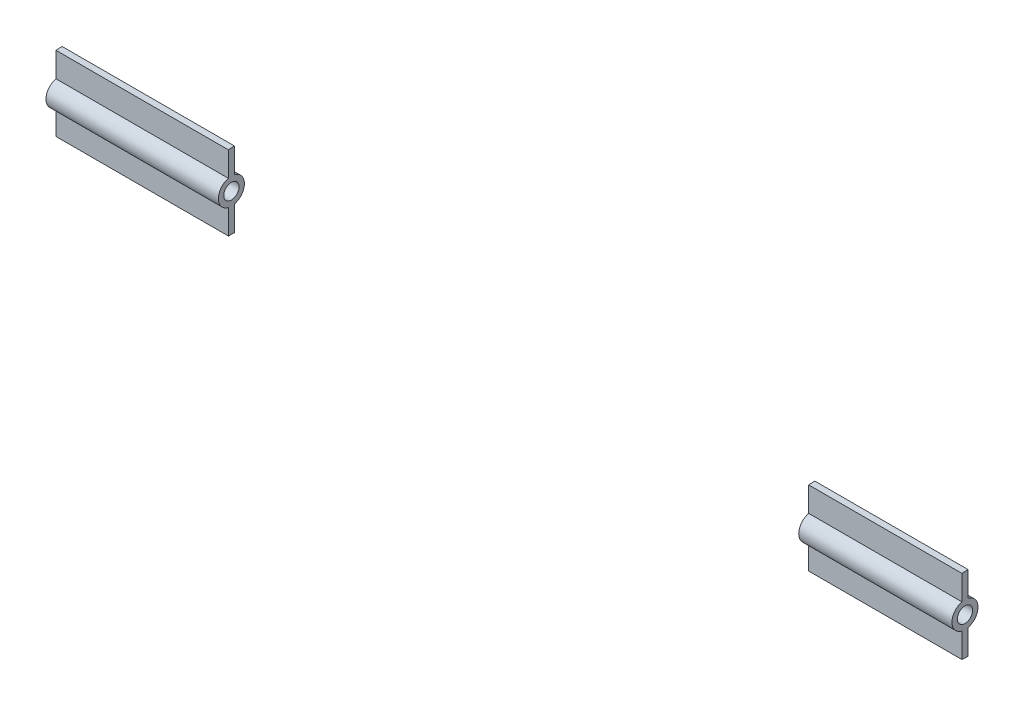
SolidWorks part; units mm, degrees
material "ABS"
ref_plane "Front Plane" through (0, 0, 0) normal (0, 0, 1) x (1, 0, 0)
ref_plane "Top Plane" through (0, 0, 0) normal (0, 1, 0) x (1, 0, 0)
ref_plane "Right Plane" through (0, 0, 0) normal (1, 0, 0) x (0, 0, -1)
body saved out of another part "Stock-V-tail-1" rebuild error yes
ref_plane "Plane1" through (235.5, 0, 0) normal (1, 0, 0) x (0, 0, -1)
sketch "Sketch2" plane through (235.5, 0, 0) normal (1, 0, 0) x (0, 0, -1)
  arc A1 (-136.0381, -9.253) -> (-136.0381, 9.253) centre (-141.8338, 0) ccw construction
  arc A3 (-136.0381, -9.253) -> (-136.0381, 9.253) centre (-141.8338, 0) ccw
  circle A4 centre (-62, 0) radius 9 construction
  circle A5 centre (-62, 0) radius 9
  spline S0 degree 3 poles (-248, 0) (-248, 0.0474) (-245.7346, 0.2359) (-243.4112, 0.6292) (-237.7674, 1.2323) (-230.8332, 1.9808) (-221.7981, 2.8592) (-211.1903, 3.8286) (-199.0563, 4.8702) (-185.65, 5.9536) (-171.1852, 7.0355) (-155.914, 8.0839) (-140.0967, 9.0504) (-124.0041, 9.8942) (-107.9109, 10.5652) (-94.6227, 10.9527) (-84.1989, 11.1308) (-76.6156, 11.194) (-69.2347, 11.1852) (-62.0877, 11.0901) (-55.2058, 10.9234) (-48.6191, 10.6715) (-42.3552, 10.3437) (-36.4402, 9.9323) (-30.8991, 9.4444) (-25.7573, 8.8756) (-21.0365, 8.2367) (-16.7549, 7.5443) (-12.9305, 6.8014) (-9.5757, 6.0106) (-6.7064, 5.1453) (-4.3287, 4.1895) (-2.4645, 3.1349) (-1.1239, 2.0336) (-0.2866, 1.0243) (0.1173, 0) (-0.2866, -1.0243) (-1.1239, -2.0336) (-2.4645, -3.1349) (-4.3287, -4.1895) (-6.7064, -5.1453) (-9.5757, -6.0106) (-12.9305, -6.8014) (-16.7549, -7.5443) (-21.0365, -8.2367) (-25.7573, -8.8756) (-30.8991, -9.4444) (-36.4402, -9.9323) (-42.3552, -10.3437) (-48.6191, -10.6715) (-55.2058, -10.9234) (-62.0877, -11.0901) (-69.2347, -11.1852) (-76.6156, -11.194) (-84.1989, -11.1308) (-94.6227, -10.9527) (-107.9109, -10.5652) (-124.0041, -9.8942) (-140.0967, -9.0504) (-155.914, -8.0839) (-171.1852, -7.0355) (-185.65, -5.9536) (-199.0563, -4.8702) (-211.1903, -3.8286) (-221.7981, -2.8592) (-230.8332, -1.9808) (-237.7674, -1.2323) (-243.4112, -0.6292) (-245.7346, -0.2359) (-248, -0.0474) (-248, 0) (-248, 0.0474) (-245.7346, 0.2359) knots -0.002133 0 0 0 0.002133 0.008488 0.018944 0.033319 0.051356 0.072756 0.097141 0.124097 0.153163 0.183834 0.215589 0.247878 0.280151 0.31186 0.327333 0.342463 0.357187 0.371448 0.385183 0.398331 0.410845 0.422673 0.433769 0.44409 0.453589 0.46224 0.47001 0.476871 0.482833 0.487909 0.492155 0.495592 0.498196 0.5 0.501804 0.504408 0.507845 0.512091 0.517167 0.523129 0.52999 0.53776 0.546411 0.55591 0.566231 0.577327 0.589155 0.601669 0.614817 0.628552 0.642813 0.657537 0.672667 0.68814 0.719849 0.752122 0.784411 0.816166 0.846837 0.875903 0.902859 0.927244 0.948644 0.966681 0.981056 0.991512 0.997867 1 1 1 1.002133 1.008488 1.018944 only from (-136.0381, 9.253) to (-136.0381, -9.253) construction
  spline S1 degree 3 poles (-136.0381, 9.253) (-132.0261, 9.4717) (-122.621, 9.9519) (-107.9109, 10.5652) (-94.6227, 10.9527) (-84.1989, 11.1308) (-76.6156, 11.194) (-69.2347, 11.1852) (-62.0877, 11.0901) (-55.2058, 10.9234) (-48.6191, 10.6715) (-42.3552, 10.3437) (-36.4402, 9.9323) (-30.8991, 9.4444) (-25.7573, 8.8756) (-21.0365, 8.2367) (-16.7549, 7.5443) (-12.9305, 6.8014) (-9.5757, 6.0106) (-6.7064, 5.1453) (-4.3287, 4.1895) (-2.4645, 3.1349) (-1.1239, 2.0336) (-0.2866, 1.0243) (0.1173, 0) (-0.2866, -1.0243) (-1.1239, -2.0336) (-2.4645, -3.1349) (-4.3287, -4.1895) (-6.7064, -5.1453) (-9.5757, -6.0106) (-12.9305, -6.8014) (-16.7549, -7.5443) (-21.0365, -8.2367) (-25.7573, -8.8756) (-30.8991, -9.4444) (-36.4402, -9.9323) (-42.3552, -10.3437) (-48.6191, -10.6715) (-55.2058, -10.9234) (-62.0877, -11.0901) (-69.2347, -11.1852) (-76.6156, -11.194) (-84.1989, -11.1308) (-94.6227, -10.9527) (-107.9109, -10.5652) (-122.621, -9.9519) (-132.0261, -9.4717) (-136.0381, -9.253) knots 0.223863 0.223863 0.223863 0.223863 0.247878 0.280151 0.31186 0.327333 0.342463 0.357187 0.371448 0.385183 0.398331 0.410845 0.422673 0.433769 0.44409 0.453589 0.46224 0.47001 0.476871 0.482833 0.487909 0.492155 0.495592 0.498196 0.5 0.501804 0.504408 0.507845 0.512091 0.517167 0.523129 0.52999 0.53776 0.546411 0.55591 0.566231 0.577327 0.589155 0.601669 0.614817 0.628552 0.642813 0.657537 0.672667 0.68814 0.719849 0.752122 0.776137 0.776137 0.776137 0.776137
extrude "Boss-Extrude1" add sketch "Sketch2" along normal up to surface (1 mm away) rebuild error yes
sketch "Sketch4" plane through (236.5, 0, 0) normal (1, 0, 0) x (0, 0, -1)
  line L0 (-117, 9.7778) -> (-117, -9.7778) construction
  line L1 (-117.8, 9.7438) -> (-117.8, 3.3045)
  line L2 (-116.2, 9.8114) -> (-116.2, 3.3045)
  line L3 (-117.8, 9.7438) -> (-116.2, 9.8114)
  line L4 (-116.2, -9.8114) -> (-116.2, -3.3045)
  line L5 (-117.8, -9.7438) -> (-117.8, -3.3045)
  line L6 (-116.2, -9.8114) -> (-117.8, -9.7438)
  circle A4 centre (-62, 0) radius 9 construction
  circle A5 centre (-62, 0) radius 9 construction
  circle A6 centre (-117, 0) radius 2
  arc A7 (-116.2, -3.3045) -> (-116.2, 3.3045) centre (-117, 0) ccw
  arc A8 (-117.8, 3.3045) -> (-117.8, -3.3045) centre (-117, 0) ccw
  spline S7 degree 1 poles (-136.0163, 8.8536) (-136.0163, -8.8536) knots 0 0 1 1 construction
  spline S8 degree 3 poles (-136.0163, 8.8536) (-130.2514, 9.1678) (-124.2459, 9.4651) (-118.1056, 9.7307) (-117.6666, 9.7495) (-117.4, 9.7609) (-117.1333, 9.7722) (-116.8666, 9.7835) (-116.6, 9.7947) (-116.3333, 9.8058) (-111.2706, 10.0168) (-100.5041, 10.4086) (-84.0958, 10.7773) (-69.6656, 10.8196) (-58.1244, 10.6127) (-49.4737, 10.3215) (-40.8313, 9.8647) (-33.6424, 9.3078) (-27.907, 8.7199) (-23.6162, 8.1931) (-19.3389, 7.5713) (-15.0835, 6.8329) (-11.5652, 6.0893) (-8.7915, 5.3615) (-6.7466, 4.7182) (-4.7593, 3.9358) (-2.8953, 2.9508) (-1.5069, 1.8551) (-0.7638, 0.969) (-0.4573, 0.3737) (-0.3714, 0) (-0.4573, -0.3737) (-0.7638, -0.969) (-1.5069, -1.8551) (-2.8953, -2.9508) (-4.7593, -3.9358) (-6.7466, -4.7182) (-8.7915, -5.3615) (-11.5652, -6.0893) (-15.0835, -6.8329) (-19.3389, -7.5713) (-23.6162, -8.1931) (-27.907, -8.7199) (-33.6424, -9.3078) (-40.8313, -9.8647) (-49.4737, -10.3215) (-58.1244, -10.6127) (-69.6656, -10.8196) (-84.0958, -10.7773) (-100.5041, -10.4086) (-111.2706, -10.0168) (-116.3333, -9.8058) (-116.6, -9.7947) (-116.8666, -9.7835) (-117.1333, -9.7722) (-117.4, -9.7609) (-117.6666, -9.7495) (-118.1056, -9.7307) (-124.2459, -9.4651) (-130.2514, -9.1678) (-136.0163, -8.8536) knots 0 0 0 0 0.0625 0.065089 0.066534 0.067256 0.067979 0.069423 0.070146 0.070868 0.072313 0.125 0.1875 0.25 0.28125 0.3125 0.34375 0.375 0.390625 0.40625 0.421875 0.4375 0.453125 0.460938 0.46875 0.476562 0.484375 0.492188 0.496094 0.498047 0.5 0.501953 0.503906 0.507812 0.515625 0.523438 0.53125 0.539062 0.546875 0.5625 0.578125 0.59375 0.609375 0.625 0.65625 0.6875 0.71875 0.75 0.8125 0.875 0.927687 0.929132 0.929854 0.930577 0.932021 0.932744 0.933466 0.934911 0.9375 1 1 1 1 construction
  spline S13 degree 3 poles (-1848.5448, 5455.4948) (-1254.8548, -370.5463) (-691.9533, -13.7835) (-107.9109, 10.5652) (-94.6227, 10.9527) (-84.1989, 11.1308) (-76.6156, 11.194) (-69.2347, 11.1852) (-62.0877, 11.0901) (-55.2058, 10.9234) (-48.6191, 10.6715) (-42.3552, 10.3437) (-36.4402, 9.9323) (-30.8991, 9.4444) (-25.7573, 8.8756) (-21.0365, 8.2367) (-16.7549, 7.5443) (-12.9305, 6.8014) (-9.5757, 6.0106) (-6.7064, 5.1453) (-4.3287, 4.1895) (-2.4645, 3.1349) (-1.1239, 2.0336) (-0.2866, 1.0243) (0.1173, 0) (-0.2866, -1.0243) (-1.1239, -2.0336) (-2.4645, -3.1349) (-4.3287, -4.1895) (-6.7064, -5.1453) (-9.5757, -6.0106) (-12.9305, -6.8014) (-16.7549, -7.5443) (-21.0365, -8.2367) (-25.7573, -8.8756) (-30.8991, -9.4444) (-36.4402, -9.9323) (-42.3552, -10.3437) (-48.6191, -10.6715) (-55.2058, -10.9234) (-62.0877, -11.0901) (-69.2347, -11.1852) (-76.6156, -11.194) (-84.1989, -11.1308) (-94.6227, -10.9527) (-107.9109, -10.5652) (-691.9613, 13.7839) (-1254.8704, 370.5562) (-1848.5696, -5455.7381) knots -6.166881 -6.166881 -6.166881 -6.166881 0.043484 0.10192 0.159336 0.187352 0.214748 0.241409 0.267232 0.292102 0.315909 0.338567 0.359984 0.380076 0.398764 0.415965 0.431629 0.445697 0.45812 0.468916 0.478106 0.485795 0.492019 0.496734 0.5 0.503266 0.507981 0.514205 0.521894 0.531084 0.54188 0.554303 0.568371 0.584035 0.601236 0.619924 0.640016 0.661433 0.684091 0.707898 0.732768 0.758591 0.785252 0.812648 0.840664 0.89808 0.956516 7.166968 7.166968 7.166968 7.166968 only from (-136.0381, 9.253) to (-136.0381, -9.253)
  spline S14 degree 3 poles (-136.0381, 9.253) (-132.0261, 9.4717) (-122.621, 9.9519) (-107.9109, 10.5652) (-94.6227, 10.9527) (-84.1989, 11.1308) (-76.6156, 11.194) (-69.2347, 11.1852) (-62.0877, 11.0901) (-55.2058, 10.9234) (-48.6191, 10.6715) (-42.3552, 10.3437) (-36.4402, 9.9323) (-30.8991, 9.4444) (-25.7573, 8.8756) (-21.0365, 8.2367) (-16.7549, 7.5443) (-12.9305, 6.8014) (-9.5757, 6.0106) (-6.7064, 5.1453) (-4.3287, 4.1895) (-2.4645, 3.1349) (-1.1239, 2.0336) (-0.2866, 1.0243) (0.1173, 0) (-0.2866, -1.0243) (-1.1239, -2.0336) (-2.4645, -3.1349) (-4.3287, -4.1895) (-6.7064, -5.1453) (-9.5757, -6.0106) (-12.9305, -6.8014) (-16.7549, -7.5443) (-21.0365, -8.2367) (-25.7573, -8.8756) (-30.8991, -9.4444) (-36.4402, -9.9323) (-42.3552, -10.3437) (-48.6191, -10.6715) (-55.2058, -10.9234) (-62.0877, -11.0901) (-69.2347, -11.1852) (-76.6156, -11.194) (-84.1989, -11.1308) (-94.6227, -10.9527) (-107.9109, -10.5652) (-122.621, -9.9519) (-132.0261, -9.4717) (-136.0381, -9.253) knots 0 0 0 0 0.043484 0.10192 0.159336 0.187352 0.214748 0.241409 0.267232 0.292102 0.315909 0.338567 0.359984 0.380076 0.398764 0.415965 0.431629 0.445697 0.45812 0.468916 0.478106 0.485795 0.492019 0.496734 0.5 0.503266 0.507981 0.514205 0.521894 0.531084 0.54188 0.554303 0.568371 0.584035 0.601236 0.619924 0.640016 0.661433 0.684091 0.707898 0.732768 0.758591 0.785252 0.812648 0.840664 0.89808 0.956516 1 1 1 1 construction
  dimension "D1" = 55
  dimension "D2" = 4
  dimension "D3" = 6.8
  dimension "D9" = 6.5069
  dimension "D5" = 0.8
  dimension "D6" = 0.8
  dimension "D7" = 0.8
  dimension "D8" = 0.8
  dimension "D4" = 0.4
extrude "Cut-Extrude2" cut sketch "Sketch4" against normal blind 44 contours A6 rebuild error yes
extrude "Boss-Extrude3" add sketch "Sketch4<4>" against normal blind 40
sketch "Sketch4<4>" plane through (236.5, 0, 0) normal (1, 0, 0) x (0, 0, -1) same geometry as "Sketch4"
sketch "Sketch9" plane through (0, 0, 0) normal (-1, 0, 0) x (0, 0, 1)
  line L0 (116.2, 9.8115) -> (116.2, 3.3045)
  line L1 (117, 9.778) -> (117, -9.7778) construction
  line L2 (117.8, 9.744) -> (117.8, 3.3045)
  line L3 (117.8, -9.7438) -> (117.8, -3.3045)
  line L4 (117.8, -3.3045) -> (117.8, -9.7438) construction
  line L5 (116.2, -9.8114) -> (116.2, -3.3045)
  line L6 (116.2, -9.8114) -> (117.8, -9.7438)
  line L7 (116.2, 9.8115) -> (117.8, 9.744)
  circle A0 centre (62, 0) radius 9 construction
  circle A1 centre (62, 0) radius 9 construction
  circle A2 centre (117, 0) radius 2
  arc A3 (116.2, 3.3045) -> (116.2, -3.3045) centre (117, 0) ccw
  arc A4 (117.8, -3.3045) -> (117.8, 3.3045) centre (117, 0) ccw
  spline S0 degree 3 poles (245.7346, 0.2359) (248.5694, 0) (245.7346, -0.2359) (243.4112, -0.6292) (237.7674, -1.2323) (230.8332, -1.9808) (221.7981, -2.8592) (211.1903, -3.8286) (199.0563, -4.8702) (185.65, -5.9536) (171.1852, -7.0355) (155.914, -8.0839) (140.0967, -9.0504) (124.0041, -9.8942) (107.9109, -10.5652) (94.6227, -10.9527) (84.1989, -11.1308) (76.6156, -11.194) (69.2347, -11.1852) (62.0877, -11.0901) (55.2058, -10.9234) (48.6191, -10.6715) (42.3552, -10.3437) (36.4402, -9.9323) (30.8991, -9.4444) (25.7573, -8.8756) (21.0365, -8.2367) (16.7549, -7.5443) (12.9305, -6.8014) (9.5757, -6.0106) (6.7064, -5.1453) (4.3287, -4.1895) (2.4645, -3.1349) (1.1239, -2.0336) (0.2866, -1.0243) (-0.1173, 0) (0.2866, 1.0243) (1.1239, 2.0336) (2.4645, 3.1349) (4.3287, 4.1895) (6.7064, 5.1453) (9.5757, 6.0106) (12.9305, 6.8014) (16.7549, 7.5443) (21.0365, 8.2367) (25.7573, 8.8756) (30.8991, 9.4444) (36.4402, 9.9323) (42.3552, 10.3437) (48.6191, 10.6715) (55.2058, 10.9234) (62.0877, 11.0901) (69.2347, 11.1852) (76.6156, 11.194) (84.1989, 11.1308) (94.6227, 10.9527) (107.9109, 10.5652) (124.0041, 9.8942) (140.0967, 9.0504) (155.914, 8.0839) (171.1852, 7.0355) (185.65, 5.9536) (199.0563, 4.8702) (211.1903, 3.8286) (221.7981, 2.8592) (230.8332, 1.9808) (237.7674, 1.2323) (243.4112, 0.6292) (245.7346, 0.2359) (248.5694, 0) (245.7346, -0.2359) knots -0.018944 -0.008488 -0.002133 0 0.002133 0.008488 0.018944 0.033319 0.051356 0.072756 0.097141 0.124097 0.153163 0.183834 0.215589 0.247878 0.280151 0.31186 0.327333 0.342463 0.357187 0.371448 0.385183 0.398331 0.410845 0.422673 0.433769 0.44409 0.453589 0.46224 0.47001 0.476871 0.482833 0.487909 0.492155 0.495592 0.498196 0.5 0.501804 0.504408 0.507845 0.512091 0.517167 0.523129 0.52999 0.53776 0.546411 0.55591 0.566231 0.577327 0.589155 0.601669 0.614817 0.628552 0.642813 0.657537 0.672667 0.68814 0.719849 0.752122 0.784411 0.816166 0.846837 0.875903 0.902859 0.927244 0.948644 0.966681 0.981056 0.991512 0.997867 1 1.002133 1.008488 1.018944 only from (136.0381, -9.253) to (2.8836, -3.3417) construction
  spline S1 degree 3 poles (192.2839, -4935.15) (-437.4026, -273.2312) (-203.4761, -2.8895) (46.7948, 10.5757) (50.5856, 10.7462) (54.3777, 10.8862) (58.1708, 10.9958) (61.9646, 11.0788) (65.7587, 11.1394) (69.5532, 11.1767) (73.3479, 11.1902) (77.1425, 11.1831) (82.2019, 11.1495) (88.5259, 11.0644) (96.1134, 10.9008) (103.6996, 10.682) (111.2843, 10.415) (118.8673, 10.105) (126.4485, 9.7546) (679.5818, -18.5145) (1215.9766, -312.6225) (1799.4173, 4425.6222) knots -0.926959 -0.926959 -0.926959 -0.926959 0.596196 0.603961 0.611727 0.619492 0.627258 0.635023 0.642789 0.650554 0.65832 0.666085 0.673851 0.689381 0.704912 0.720443 0.735974 0.751505 0.767036 0.782567 4.151766 4.151766 4.151766 4.151766 only from (41.7583, 10.2894) to (136.0384, 9.2532) construction
  spline S2 degree 3 poles (136.0381, -9.253) (132.0261, -9.4717) (122.621, -9.9519) (107.9109, -10.5651) (94.6227, -10.9527) (84.1989, -11.1308) (76.6156, -11.1939) (69.2347, -11.1851) (62.0877, -11.0901) (55.2059, -10.9233) (48.6192, -10.6714) (42.3553, -10.3436) (36.4402, -9.9323) (30.8991, -9.4443) (25.7574, -8.8755) (21.0365, -8.2366) (16.755, -7.5442) (12.9306, -6.8013) (9.5758, -6.0105) (6.7064, -5.1452) (4.5144, -4.2641) (3.317, -3.6131) (2.8836, -3.3417) knots 0.223863 0.223863 0.223863 0.223863 0.247878 0.280151 0.31186 0.327333 0.342463 0.357187 0.371448 0.385183 0.398331 0.410845 0.422673 0.433769 0.44409 0.453589 0.46224 0.47001 0.476871 0.482833 0.487909 0.490962 0.490962 0.490962 0.490962 construction
  spline S3 degree 3 poles (41.7583, 10.2894) (42.1741, 10.3154) (43.8526, 10.4174) (46.7948, 10.5757) (50.5856, 10.7462) (54.3777, 10.8862) (58.1708, 10.9958) (61.9646, 11.0788) (65.7587, 11.1394) (69.5532, 11.1767) (73.3479, 11.1902) (77.1425, 11.1831) (82.2019, 11.1495) (88.5259, 11.0644) (96.1134, 10.9008) (103.6996, 10.682) (111.2843, 10.415) (118.8673, 10.105) (126.4485, 9.7546) (132.1718, 9.4621) (135.3681, 9.2897) (136.0384, 9.2532) knots 0.593638 0.593638 0.593638 0.593638 0.596196 0.603961 0.611727 0.619492 0.627258 0.635023 0.642789 0.650554 0.65832 0.666085 0.673851 0.689381 0.704912 0.720443 0.735974 0.751505 0.767036 0.782567 0.786688 0.786688 0.786688 0.786688 construction
  spline S4 degree 1 poles (136.0163, -8.8536) (3.096, -3.0027) knots 0 0 1 1 construction
  spline S5 degree 3 poles (136.0163, -8.8536) (130.4401, -9.1575) (124.4346, -9.4558) (118.2944, -9.7226) (117.6666, -9.7495) (117.4, -9.7609) (117.1333, -9.7722) (116.8666, -9.7835) (116.6, -9.7947) (116.3333, -9.8058) (111.6482, -10.0011) (101.4484, -10.3761) (85.7962, -10.749) (69.0464, -10.8405) (55.0925, -10.5595) (43.9416, -10.049) (35.5909, -9.4841) (27.2619, -8.6876) (18.9753, -7.5607) (12.1254, -6.2915) (6.7787, -4.796) (4.2528, -3.7273) (3.096, -3.0027) knots 0.223863 0.223863 0.223863 0.223863 0.25725 0.25981 0.260608 0.261007 0.261406 0.262204 0.262603 0.263002 0.2638 0.290638 0.324025 0.357412 0.3908 0.407493 0.424187 0.440881 0.457574 0.474268 0.482615 0.490962 0.490962 0.490962 0.490962 construction
  spline S6 degree 1 poles (41.7832, 9.8901) (136.0166, 8.8538) knots 0 0 1 1 construction
  spline S7 degree 3 poles (41.7832, 9.8901) (49.6219, 10.3806) (65.3277, 10.8752) (88.9017, 10.7449) (105.7909, 10.2326) (114.9551, 9.8634) (116.3333, 9.806) (116.6, 9.7948) (116.8666, 9.7836) (117.1333, 9.7723) (117.4, 9.761) (117.6666, 9.7497) (123.8737, 9.4839) (130.0129, 9.181) (136.0166, 8.8538) knots 0.593638 0.593638 0.593638 0.593638 0.6419 0.690163 0.738425 0.745667 0.746486 0.746896 0.747306 0.748125 0.748535 0.748945 0.749764 0.786688 0.786688 0.786688 0.786688 construction
  dimension "D2" = 4
  dimension "D1" = 0.4
extrude "Cut-Extrude4" cut sketch "Sketch9" against normal blind 44 contours A2 rebuild error yes
extrude "Boss-Extrude4" add sketch "Sketch9<3>" against normal blind 45 contours L3 A4 L2 L7 L0 A3 L5 L6 A2 region at (0, 9.5703, 116.9912)
sketch "Sketch9<3>" plane through (0, 0, 0) normal (-1, 0, 0) x (0, 0, 1) same geometry as "Sketch9"
